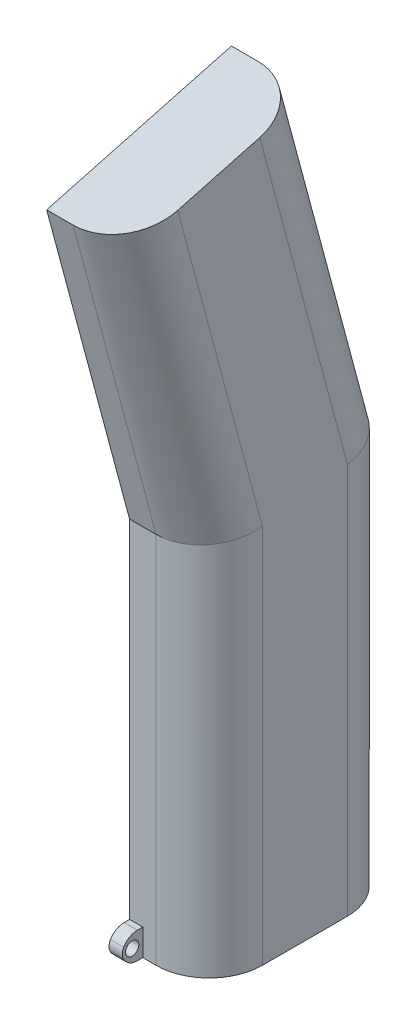
SolidWorks part; units mm, degrees
ref_plane "Front Plane" through (0, 0, 0) normal (0, 0, 1) x (1, 0, 0)
ref_plane "Top Plane" through (0, 0, 0) normal (0, 1, 0) x (1, 0, 0)
ref_plane "Right Plane" through (0, 0, 0) normal (1, 0, 0) x (0, 0, -1)
sketch "Sketch3" plane through (0, 0, 0) normal (1, 0, 0) x (0, 0, -1)
  line L1 (-18, 0) -> (18, 0)
  line L2 (-18, 0) -> (-18, 70.2605)
  line L4 (18, 0) -> (18, 75)
  line L5 (18, 75) -> (1.1768, 137.7852)
  line L6 (-18, 70.2605) -> (-33.5966, 128.4677)
  line L7 (1.1768, 137.7852) -> (-33.5966, 128.4677)
  point P4 (0, 0)
  dimension "D1" = 36
  dimension "D2" = 75
  dimension "D3" = 75
  dimension "D4" = 36
  dimension "D5" = 65
extrude "Boss-Extrude2" add sketch "Sketch3" along normal blind 15
fillet "Fillet1" radius 10 4 edges at (15, 35.1303, 18) (15, 99.3641, 25.7983) (15, 106.3926, -9.5884) (15, 37.5, -18)
shell "Shell1" thickness 2 removed face at (0, 68.5856, 5.4033)
sketch "Sketch4" plane through (0, 0, 0) normal (0, -1, 0) x (1, 0, 0)
  line L0 (0, 18) -> (0, -18) construction
  line L1 (0, -3.1) -> (0, 3.1)
  arc A0 (0, -3.1) -> (0, 3.1) centre (0, 0) ccw
  dimension "D1" = 6.2
extrude "Cut-Extrude1" cut sketch "Sketch4" against normal up to next
sketch "Sketch5" plane through (0, 0, 18) normal (0, 0, 1) x (1, 0, 0)
  line L1 (0, 0) -> (2.5, 0)
  line L2 (0, 0) -> (0, 5)
  line L3 (0, 5) -> (2.5, 5)
  line L4 (2.5, 0) -> (2.5, 5)
  point P4 (0, 0)
  point P6 (2.5, 0.8372)
  point P7 (0, 0)
  dimension "D1" = 2.5
  dimension "D2" = 5
extrude "Boss-Extrude3" add sketch "Sketch5" along normal blind 4
sketch "Sketch6" plane through (2.5, 0, 0) normal (1, 0, 0) x (0, 0, -1)
  line L0 (-18, 0) -> (-18, 5) construction
  line L1 (-22, 5) -> (-18, 5) construction
  circle A0 centre (-20, 2.5) radius 1.25
  point P4 (-18, 2.5)
  point P5 (0, 0)
  point P8 (-20, 5)
  dimension "D1" = 2.5
extrude "Cut-Extrude2" cut sketch "Sketch6" against normal up to next
fillet "Fillet2" radius 3 2 edges at (1.25, 0, 22) (1.25, 5, 22)
fillet "Fillet3" radius 2 1 edges at (1.25, 2.5, 21.958)
mirror "Mirror1" about plane through (0, 0, 0) normal (0, 0, 1) of "Cut-Extrude2", "Fillet2", "Fillet3", "Boss-Extrude3"
